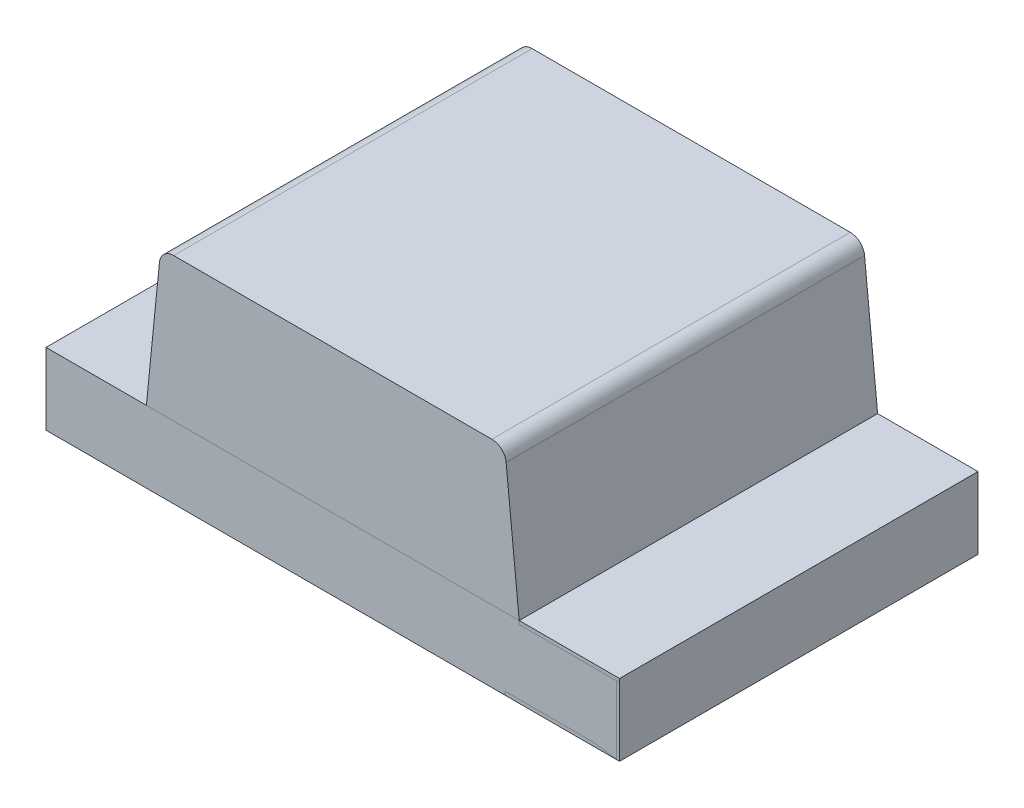
SolidWorks part; units mm, degrees
note: The reader was unsure of these and kept them because the rebuilt part matched: shared geometry of "Sketch1<3>", "Sketch2<3>".
other "DetailItem1"
ref_plane "Front Plane" through (0, 0, 0) normal (0, 0, 1) x (1, 0, 0)
ref_plane "Top Plane" through (0, 0, 0) normal (0, 1, 0) x (1, 0, 0)
ref_plane "Right Plane" through (0, 0, 0) normal (1, 0, 0) x (0, 0, -1)
sketch "Sketch1" plane through (0, 0, 0) normal (0, 0, 1) x (1, 0, 0)
  line L0 (-1, 0.125) -> (1, -0.125) construction
  line L1 (-1, 0.125) -> (1, 0.125)
  line L2 (-1, 0.125) -> (-1, -0.125)
  line L3 (-1, -0.125) -> (1, -0.125)
  line L4 (1, 0.125) -> (1, -0.125)
  line L5 (-0.6, 0.625) -> (-0.65, 0.125)
  line L6 (-0.65, 0.125) -> (0.65, 0.125)
  line L7 (0.65, 0.125) -> (0.6, 0.625)
  line L8 (0.6, 0.625) -> (-0.6, 0.625)
  line L9 (0, 0.625) -> (0, 0.125) construction
  dimension "D1" = 0.25
  dimension "D2" = 2
  dimension "D3" = 1.3
  dimension "D4" = 1.2
  dimension "D5" = 0.75
extrude "Extrude1" add sketch "Sketch1" along normal mid plane 1.25 contours L4 L1 L2 L3
extrude "Extrude2" add sketch "Sketch1<3>" along normal mid plane 1.25 separate body contours L7 L8 L5 L1
sketch "Sketch1<3>" plane through (0, 0, 0) normal (0, 0, 1) x (1, 0, 0) same geometry as "Sketch1"
sketch "Sketch2" plane through (0, -0.125, 0) normal (0, -1, 0) x (1, 0, 0)
  line L0 (-1, -0.625) -> (1, -0.625) construction
  line L1 (-1, 0.625) -> (-0.6, 0.625)
  line L2 (-1, 0.625) -> (-1, -0.625)
  line L3 (-1, -0.625) -> (-0.6, -0.625)
  line L4 (-0.6, 0.625) -> (-0.6, -0.625)
  line L5 (0, 0) -> (0, 0.625) construction
  line L6 (-1, 0.625) -> (1, 0.625) construction
  line L7 (0.6, 0.625) -> (0.6, -0.625)
  line L8 (1, -0.625) -> (0.6, -0.625)
  line L9 (1, 0.625) -> (1, -0.625)
  line L10 (1, 0.625) -> (0.6, 0.625)
  line L11 (-0.3398, 0.625) -> (-0.3398, -0.625)
  line L12 (-0.3398, -0.625) -> (0.3253, 0)
  line L13 (0.6, 0) -> (-0.6, 0) construction
  line L14 (0.3253, 0) -> (-0.3398, 0.625)
  line M1 (-1, -0.625) -> (1, -0.625)
  line M2 (1, -0.625) -> (1, 0.625)
  line M3 (1, 0.625) -> (-1, 0.625)
  line M4 (-1, 0.625) -> (-1, -0.625)
  dimension "D1" = 0.4
sketch "Sketch3" plane through (0, 0.125, 0) normal (0, 1, 0) x (-1, 0, 0)
  line L0 (-1, 0.625) -> (-0.6, 0.625) construction
  line L1 (1, -0.625) -> (0.65, -0.625)
  line L2 (1, -0.625) -> (1, 0.625)
  line L3 (1, 0.625) -> (0.65, 0.625)
  line L4 (0.65, -0.625) -> (0.65, 0.625)
  line L5 (-1, -0.625) -> (-0.65, -0.625)
  line L6 (-1, -0.625) -> (-1, 0.625)
  line L7 (-1, 0.625) -> (-0.65, 0.625)
  line L8 (-0.65, -0.625) -> (-0.65, 0.625)
  line L9 (-0.65, 0.625) -> (-0.65, -0.625) construction
  line M1 (-1, -0.625) -> (1, -0.625)
  line M2 (1, -0.625) -> (1, 0.625)
  line M3 (1, 0.625) -> (-1, 0.625)
  line M4 (-1, 0.625) -> (-1, -0.625)
extrude "Extrude3" add sketch "Sketch2" against normal blind 0.013 and the other way blind 0.0001 separate body
extrude "Extrude4" add sketch "Sketch2<3>" against normal blind 0.012 and the other way blind 0.0001 separate body contours L4 M3 M4 M1 | L7 M3 M1 M2
sketch "Sketch2<3>" plane through (0, -0.125, 0) normal (0, -1, 0) x (1, 0, 0) same geometry as "Sketch2"
extrude "Extrude5" add sketch "Sketch3" against normal blind 0.012 and the other way blind 0.0001 separate body contours L4 M1 M2 M3 | L8 M1 M3 M4
fillet "Fillet1" radius 0.05 2 edges at (0.6, 0.625, 0) (-0.6, 0.625, 0)
sketch "Sketch5" plane through (1, 0, 0) normal (1, 0, 0) x (0, 0, -1)
  line L1 (-0.625, 0.125) -> (0.625, 0.125)
  line L2 (-0.625, 0.125) -> (-0.625, -0.125)
  line L3 (-0.625, -0.125) -> (0.625, -0.125)
  line L4 (0.625, 0.125) -> (0.625, -0.125)
extrude "Extrude6" add sketch "Sketch5" against normal blind 0.01 and the other way blind 0.0001 separate body
sketch "Sketch6" plane through (-1, 0, 0) normal (-1, 0, 0) x (0, 0, 1)
  line L1 (-0.625, 0.125) -> (0.625, 0.125)
  line L2 (-0.625, 0.125) -> (-0.625, -0.1251)
  line L3 (-0.625, -0.1251) -> (0.625, -0.1251)
  line L4 (0.625, 0.125) -> (0.625, -0.1251)
extrude "Extrude7" add sketch "Sketch6" against normal blind 0.01 and the other way blind 0.0001 separate body
sketch "Sketch7" plane through (0, -0.1251, 0) normal (0, -1, 0) x (1, 0, 0)
  line L0 (-0.9164, 0.625) -> (-0.9164, -0.6146) construction
  line L1 (-0.6, 0.625) -> (-1, 0.625) construction
  text T0 "www.SunLED.com" font "Verdana" height 0.05
extrude "Cut-Extrude1" cut sketch "Sketch7" against normal blind 0.01
